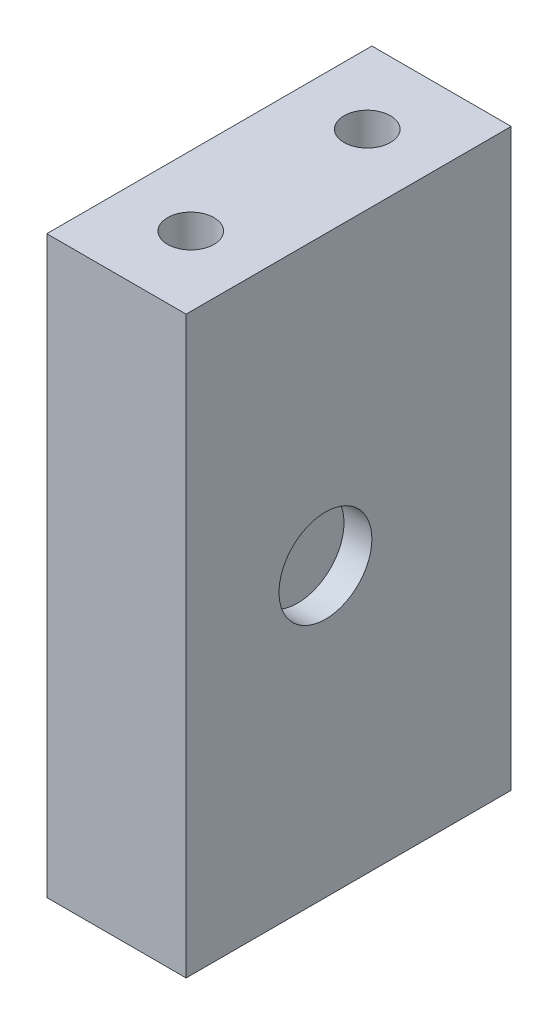
SolidWorks part; units mm, degrees
material "ABS"
ref_plane "Front Plane" through (0, 0, 0) normal (0, 0, 1) x (1, 0, 0)
ref_plane "Top Plane" through (0, 0, 0) normal (0, 1, 0) x (1, 0, 0)
ref_plane "Right Plane" through (0, 0, 0) normal (1, 0, 0) x (0, 0, -1)
sketch "Sketch1" plane through (0, 0, 0) normal (0, 1, 0) x (1, 0, 0)
  line L0 (0, 0) -> (7.5, 0) construction
  line L1 (7.5, -17.5) -> (-7.5, -17.5)
  line L2 (7.5, -17.5) -> (7.5, 17.5)
  line L3 (7.5, 17.5) -> (-7.5, 17.5)
  line L4 (-7.5, -17.5) -> (-7.5, 17.5)
  line L5 (7.5, -17.5) -> (-7.5, 17.5) construction
  line L6 (7.5, 17.5) -> (-7.5, -17.5) construction
  circle A0 centre (0, 9.5) radius 2.5
  circle A1 centre (0, -9.5) radius 2.5
  point P0 (0, 0)
  dimension "D4" = 5
  dimension "D1" = 15
  dimension "D2" = 35
  dimension "D3" = 8
extrude "Boss-Extrude1" add sketch "Sketch1" along normal mid plane 61.9
sketch "Sketch2" plane through (7.5, 0, 0) normal (1, 0, 0) x (0, 0, -1)
  line L1 (17.5, 30.95) -> (17.5, -30.95) construction
  circle A0 centre (-2.5, 0) radius 5
  dimension "D1" = 10
  dimension "D2" = 20
extrude "Cut-Extrude1" cut sketch "Sketch2" against normal blind 3
